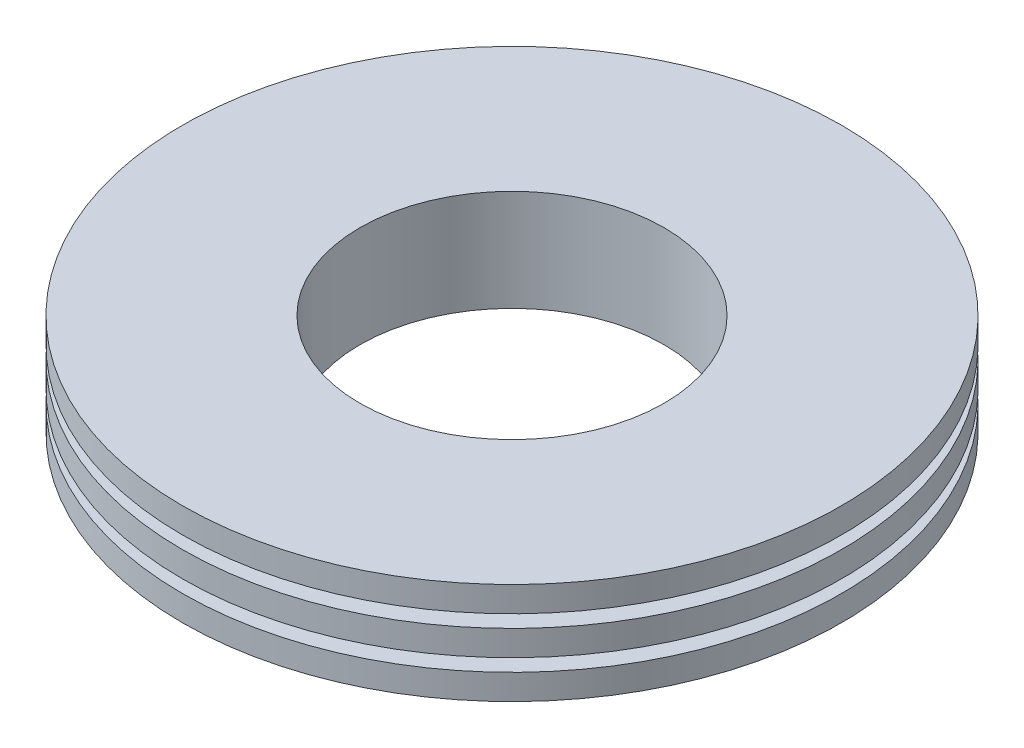
SolidWorks part; units mm, degrees
ref_plane "前视基准面" through (0, 0, 0) normal (0, 0, 1) x (1, 0, 0)
ref_plane "上视基准面" through (0, 0, 0) normal (0, 1, 0) x (1, 0, 0)
ref_plane "右视基准面" through (0, 0, 0) normal (1, 0, 0) x (0, 0, -1)
sketch "草图1" plane through (0, 0, 0) normal (0, 1, 0) x (1, 0, 0)
  circle A0 centre (0, 0) radius 13
extrude "凸台-拉伸1" add sketch "草图1" along normal blind 4
sketch "草图2" plane through (0, 0, 0) normal (0, -1, 0) x (1, 0, 0)
  circle A0 centre (0, 0) radius 6
extrude "切除-拉伸1" cut sketch "草图2" against normal blind 4
sketch "草图3" plane through (0, 0, 0) normal (0, -1, 0) x (1, 0, 0)
  circle A0 centre (0, 0) radius 13
  circle A1 centre (0, -0.1959) radius 12
extrude "切除-拉伸2" cut sketch "草图3" against normal blind 0.5 from offset 1 offset against normal yes
extrude "切除-拉伸3" cut sketch "草图3<2>" along normal blind 0.5 from offset 3 offset against normal yes
sketch "草图3<2>" plane through (0, 0, 0) normal (0, -1, 0) x (1, 0, 0) same geometry as "草图3"
